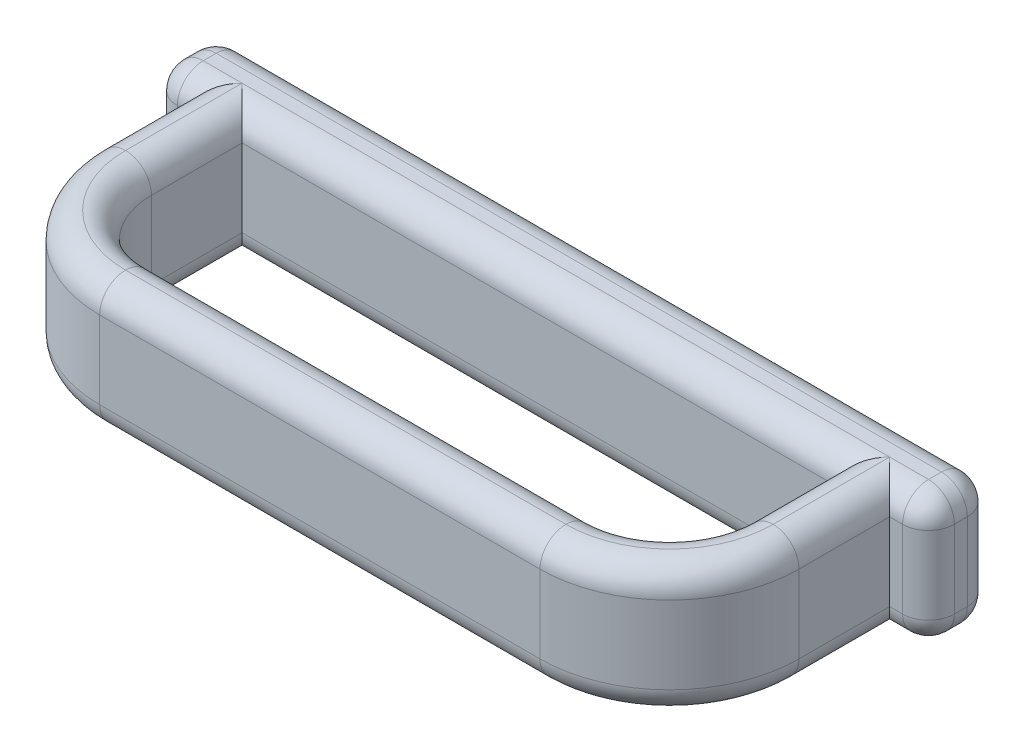
SolidWorks part; units mm, degrees
ref_plane "Front Plane" through (0, 0, 0) normal (0, 0, 1) x (1, 0, 0)
ref_plane "Top Plane" through (0, 0, 0) normal (0, 1, 0) x (1, 0, 0)
ref_plane "Right Plane" through (0, 0, 0) normal (1, 0, 0) x (0, 0, -1)
sketch "Sketch1" plane through (0, 0, 0) normal (0, 1, 0) x (1, 0, 0)
  line L1 (-30, 2.5) -> (30, 2.5)
  line L2 (-30, 2.5) -> (-30, -2.5)
  line L3 (-30, -2.5) -> (30, -2.5)
  line L4 (30, 2.5) -> (30, -2.5)
  line L5 (-30, 2.5) -> (30, -2.5) construction
  line L6 (-30, -2.5) -> (30, 2.5) construction
  point P0 (0, 0)
  dimension "D1" = 5
  dimension "D2" = 60
extrude "Boss-Extrude1" add sketch "Sketch1" along normal blind 10 contours L1 L4 L3 L2
sketch "Sketch2" plane through (0, 0, 2.5) normal (0, 0, 1) x (1, 0, 0)
  line L0 (-30, 5) -> (30, 5) construction
  line L1 (-30, 10) -> (-30, 0) construction
  line L2 (30, 10) -> (30, 0) construction
  line L3 (0, 10) -> (0, 0) construction
  line L4 (-30, 10) -> (30, 10) construction
  line L5 (-15, 10) -> (-15, 0) construction
  line L6 (-30, 0) -> (30, 0) construction
  line L7 (15, 10) -> (15, 0) construction
  line L8 (-25, 10) -> (-25, 0) construction
  line L9 (-30, 2.5) -> (-25, 2.5) construction
  line L10 (-30, 7.5) -> (-25, 7.5) construction
  line L12 (-27, 10) -> (-23, 10)
  line L13 (-27, 10) -> (-27, 0)
  line L14 (-27, 0) -> (-23, 0)
  line L15 (-23, 10) -> (-23, 0)
  line L16 (-27, 10) -> (-23, 0) construction
  line L17 (-27, 0) -> (-23, 10) construction
  point P23 (-25, 5)
  point P32 (0, 0)
  point P33 (-25, 5)
  dimension "D1" = 15
  dimension "D2" = 15
  dimension "D3" = 5
  dimension "D4" = 2.5
  dimension "D5" = 4
ref_plane "Plane1" through (0, 5, 0) normal (0, 1, 0) x (1, 0, 0)
sketch3d "3DSketch2"
  line L0 (-25, 5, 2.5) -> (-25, 5, 9.5)
  line L1 (-17, 5, 17.5) -> (17, 5, 17.5)
  line L2 (-30, 5, 2.5) -> (30, 5, 2.5) construction
  line L3 (27, 0, 4) -> (23, 0, 4) construction
  line L4 (25, 5, 2.5) -> (25, 5, 9.5)
  arc A0 (-25, 5, 9.5) -> (-17, 5, 17.5) centre (-17, 5, 9.5) ccw
  arc A1 (17, 5, 17.5) -> (25, 5, 9.5) centre (17, 5, 9.5) ccw
  point P4 (25, 5, 2.5)
  point P7 (25, 0, 4)
  point P13 (-25, 5, 17.5)
  point P14 (-17, 13, 9.5)
  point P17 (25, 5, 17.5)
  point P18 (17, 13, 9.5)
  dimension "D1" = 8
  dimension "D2" = 15
sweep "Sweep6" add profiles "Sketch2" path "3DSketch2"
fillet "Fillet1" radius 2 36 edges at (-21.2426, 0, 13.7426) (0, 0, 15.5) (21.2426, 0, 13.7426) (-24.0711, 0, 16.5711) (0, 0, 19.5) (24.0711, 0, 16.5711) (-28.5, 0, 2.5) (-27, 0, 6) (-23, 0, 6) (0, 0, 2.5) (23, 0, 6) (27, 0, 6) (28.5, 0, 2.5) (30, 0, 0) (0, 0, -2.5) (-30, 0, 0) (-24.0711, 10, 16.5711) (24.0711, 10, 16.5711) (-21.2426, 10, 13.7426) (21.2426, 10, 13.7426) (-30, 5, -2.5) (-30, 5, 2.5) (30, 5, 2.5) (30, 5, -2.5) (0, 10, -2.5) (30, 10, 0) (28.5, 10, 2.5) (27, 10, 6) (23, 10, 6) (0, 10, 2.5) (-23, 10, 6) (-27, 10, 6) (-28.5, 10, 2.5) (-30, 10, 0) (0, 10, 19.5) (0, 10, 15.5)
